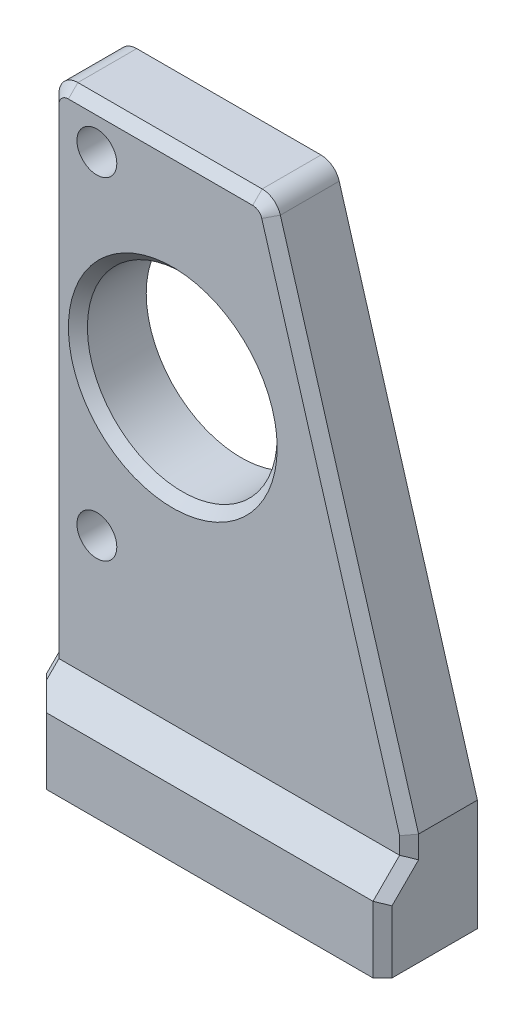
SolidWorks part; units mm, degrees
ref_plane "Ebene vorne" through (0, 0, 0) normal (0, 0, 1) x (1, 0, 0)
ref_plane "Ebene oben" through (0, 0, 0) normal (0, 1, 0) x (1, 0, 0)
ref_plane "Ebene rechts" through (0, 0, 0) normal (1, 0, 0) x (0, 0, -1)
sketch "Skizze1" plane through (0, 0, 0) normal (0, 0, 1) x (1, 0, 0)
  line L0 (0, 0) -> (71.8499, 0) construction
  line L1 (3.5487, 35) -> (89.7998, -6) construction
  line L2 (10.7739, 31.5654) -> (18.287, 47.3706) construction
  line L3 (6.9832, 42.2252) -> (14.1827, 57.3706) construction
  line L4 (14.1827, 57.3706) -> (28.287, 57.3706) construction
  line L5 (28.287, 57.3706) -> (28.287, 0)
  line L6 (28.287, 0) -> (-13.0888, 0)
  line L7 (6.9832, 42.2252) -> (0.1141, 27.7748) construction
  line L8 (0.1141, 27.7748) -> (-13.0888, 0) construction
  line L9 (-13.0888, 0) -> (-13.0888, 27.3482)
  line L10 (-13.0888, 57.3706) -> (14.1827, 57.3706) construction
  line L11 (3.5487, 35) -> (-13.0888, 42.9087) construction
  line L12 (-8.0888, 57.3706) -> (-8.0888, 15.7603) construction
  line L13 (-8.0888, 40.5319) -> (-29.0289, 40.5319) construction
  line L14 (-13.0888, 57.3706) -> (-13.0888, 62.3706)
  line L15 (-13.0888, 62.3706) -> (28.287, 62.3706)
  line L16 (28.287, 62.3706) -> (28.287, 57.3706)
  line L17 (-13.0888, 53.7156) -> (-13.0888, 27.3482)
  line L18 (-13.0888, 53.7156) -> (-13.0888, 57.3706)
  arc A0 (0, 0) -> (84.5911, 83.8491) centre (89.7998, -6) cw construction
  circle A1 centre (3.5487, 35) radius 5.5 construction
  circle A2 centre (3.5487, 35) radius 2.5 construction
  circle A3 centre (18.287, 47.3706) radius 2.25 construction
  circle A4 centre (3.2608, 15.7603) radius 2.25 construction
  arc A5 (0.1141, 27.7748) -> (6.9832, 42.2252) centre (3.5487, 35) ccw construction
  circle A7 centre (-8.0888, 23.0319) radius 2.1
  circle A8 centre (-8.0888, 58.0319) radius 2.1
  dimension "D1" = 90
  dimension "D2" = 11
  dimension "D3" = 5
  dimension "D4" = 35
  dimension "D6" = 4.5
  dimension "D12" = 4.2
  dimension "D5" = 8
  dimension "D7" = 35
  dimension "D8" = 10
  dimension "D9" = 10
  dimension "D10" = 6
  dimension "D13" = 35
  dimension "D14" = 5
  dimension "D15" = 5
extrude "Aufsatz-Linear austragen1" add sketch "Skizze1" along normal blind 10
sketch "Skizze2" plane through (0, 0, 0) normal (0, -1, 0) x (1, 0, 0)
  line L0 (-13.0888, 5) -> (28.287, 5) construction
  line L2 (28.287, 10) -> (28.287, 0) construction
  line L3 (7.5991, 5) -> (7.5991, 10) construction
  line L4 (-13.0888, 10) -> (28.287, 10) construction
  line L5 (0, 0) -> (0, 10) construction
  circle A0 centre (-7, 5) radius 1.5
  circle A2 centre (6.18, 5) radius 1.5
  circle A3 centre (19.36, 5) radius 1.5
  dimension "D1" = 3
  dimension "D2" = 7
  dimension "D3" = 6.18
  dimension "D4" = 13.18
extrude "Schnitt-Linear austragen1" cut sketch "Skizze2" against normal blind 8
sketch "Skizze4" plane through (0, 0, 10) normal (0, 0, 1) x (1, 0, 0)
  line L0 (-15.0952, 10) -> (28.287, 10)
  line L2 (28.287, 0) -> (28.287, 62.3706) construction
  line L3 (28.287, 10) -> (36.0933, 46.99)
  line L4 (36.0933, 46.99) -> (30.4291, 65.9575)
  line L5 (30.4291, 65.9575) -> (-16.081, 65.9575)
  line L6 (-16.081, 65.9575) -> (-16.081, 27.7535)
  line L7 (-16.081, 27.7535) -> (-15.0952, 10)
  line L8 (-13.0888, 0) -> (28.287, 0) construction
  dimension "D1" = 10
extrude "Schnitt-Linear austragen3" cut sketch "Skizze4" against normal blind 2.8
sketch "Skizze7" plane through (0, 0, 7.2) normal (0, 0, 1) x (1, 0, 0)
  line L0 (-8.0888, 58.0319) -> (-8.0888, 23.0319) construction
  line L1 (-8.0888, 40.5319) -> (-0.0888, 40.5319) construction
  circle A0 centre (-0.0888, 40.5319) radius 10
  dimension "D2" = 20
  dimension "D1" = 8
extrude "Schnitt-Linear austragen5" cut sketch "Skizze7" against normal through all and the other way through all
chamfer "Fase1" distance 3 angle 45 1 edges at (7.5991, 10, 10)
sketch "Skizze5" plane through (0, 0, 0) normal (0, 0, -1) x (-1, 0, 0)
  line L0 (-24.8127, 11.7368) -> (-9.8243, 62.3706)
  line L1 (-28.287, 62.3706) -> (13.0888, 62.3706) construction
  line L2 (-9.8243, 62.3706) -> (-28.287, 62.3706)
  line L3 (-28.287, 62.3706) -> (-28.287, 0)
  line L4 (-24.8127, 11.7368) -> (-24.8127, 0)
  line L5 (13.0888, 0) -> (-28.287, 0) construction
  line L6 (-24.8127, 0) -> (-28.287, 0)
extrude "Schnitt-Linear austragen4" cut sketch "Skizze5" against normal blind 10
fillet "Verrundung1" radius 2 2 edges at (-13.0888, 62.3706, 3.6) (9.8243, 62.3706, 3.6)
chamfer "Fase2" distance 1 angle 45 10 edges at (17.5305, 36.3375, 7.2) (-13.0888, 35.0853, 7.2) (9.5274, 61.973, 7.2) (-12.503, 61.7848, 7.2) (-1.3791, 62.3706, 7.2) (-13.0888, 8.4, 8.6) (24.8127, 10.7684, 7.2) (24.8127, 3.5, 10) (24.8127, 8.4, 8.6) (9.9112, 40.5319, 7.2)
chamfer "Fase3" distance 2.5 angle 45 1 edges at (-13.0888, 2.7929, 10)
sketch "Skizze8" plane through (0, 0, 0) normal (0, 0, -1) x (-1, 0, 0)
  circle A0 centre (8.0888, 23.0319) radius 3.6
  dimension "D1" = 7.2
extrude "Schnitt-Linear austragen6" cut sketch "Skizze8" against normal blind 3
chamfer "Fase4" distance 0.6 angle 45 1 edges at (-10.1888, 23.0319, 3)
